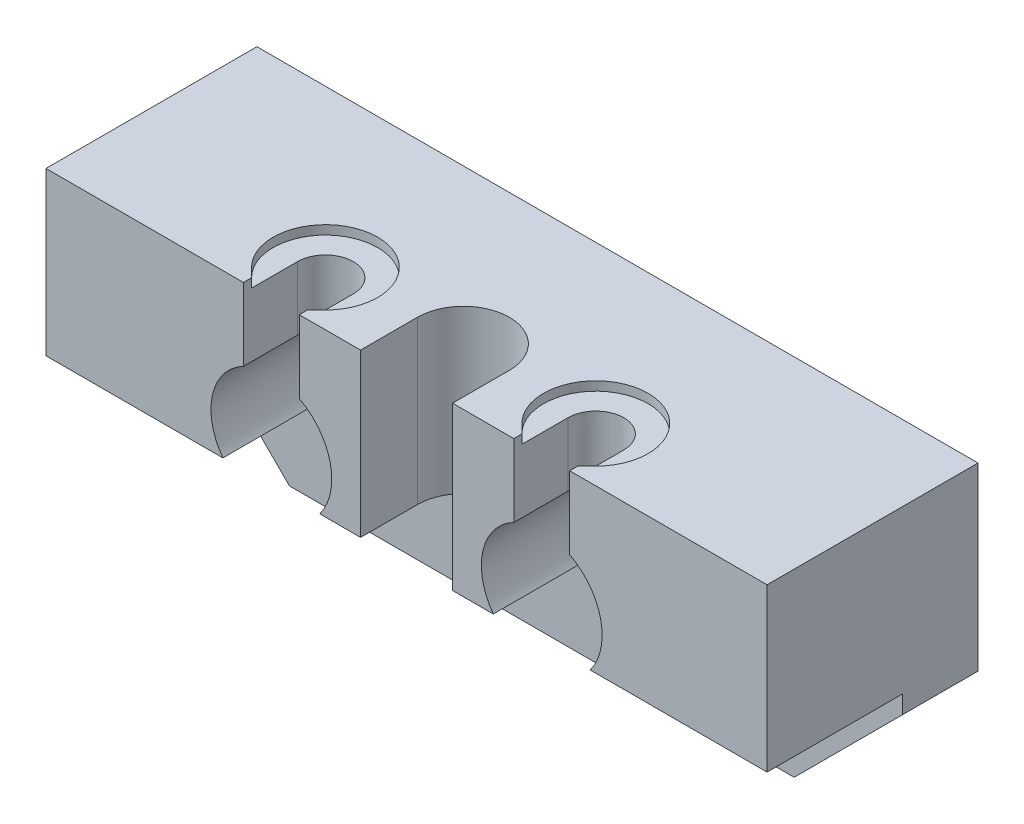
SolidWorks part; units mm, degrees
ref_plane "Front Plane" through (0, 0, 0) normal (0, 0, 1) x (1, 0, 0)
ref_plane "Top Plane" through (0, 0, 0) normal (0, 1, 0) x (1, 0, 0)
ref_plane "Right Plane" through (0, 0, 0) normal (1, 0, 0) x (0, 0, -1)
sketch "Sketch1" plane through (0, 0, 0) normal (0, 0, 1) x (1, 0, 0)
  line L1 (-20, 0) -> (20, 0)
  line L2 (-20, 0) -> (-20, 16)
  line L3 (-20, 16) -> (20, 16)
  line L4 (20, 0) -> (20, 16)
  dimension "D2" = 40
  dimension "D3" = 16
extrude "Boss-Extrude1" add sketch "Sketch1" along normal blind 12
sketch "Sketch2" plane through (0, 0, 12) normal (0, 0, 1) x (1, 0, 0)
  line L0 (0, 8) -> (0, 9) construction
  line L2 (-7.5, 9) -> (7.5, 9) construction
  line L3 (20, 16) -> (-20, 16) construction
  line L4 (-7.5, 5) -> (-7.5, 13) construction
  line L5 (-9.05, 5) -> (-9.05, 13) construction
  line L6 (-5.95, 5) -> (-5.95, 13) construction
  line L7 (7.5, 5) -> (7.5, 13) construction
  line L8 (5.95, 5) -> (5.95, 13) construction
  line L9 (9.05, 5) -> (9.05, 13) construction
  line L10 (-16, 8) -> (16, 8) construction
  arc A0 (-9.05, 5) -> (-5.95, 5) centre (-7.5, 5) ccw construction
  arc A1 (-5.95, 13) -> (-9.05, 13) centre (-7.5, 13) ccw construction
  arc A2 (5.95, 5) -> (9.05, 5) centre (7.5, 5) ccw construction
  arc A3 (9.05, 13) -> (5.95, 13) centre (7.5, 13) ccw construction
  circle A4 centre (-16, 8) radius 1.7784 construction
  circle A5 centre (16, 8) radius 1.7784 construction
  circle A6 centre (-7.5, 9) radius 1.55
  circle A7 centre (7.5, 9) radius 1.55
  point P8 (-7.5, 9)
  point P15 (7.5, 9)
  dimension "D1" = 1.55
  dimension "D2" = 8
  dimension "D3" = 7
  dimension "D4" = 15
  dimension "D5" = 1
  dimension "D6" = 32
extrude "Cut-Extrude1" cut sketch "Sketch2" against normal through all
sketch "Sketch5" plane through (0, 16, 0) normal (0, 1, 0) x (1, 0, 0)
  line L0 (0, 0) -> (0, -9) construction
  line L1 (-7.5, -9) -> (7.5, -9) construction
  line L2 (20, -12) -> (-20, -12) construction
  line L3 (-9.05, -9) -> (-9.05, -12)
  line L4 (-9.05, -12) -> (-5.95, -12)
  line L5 (-5.95, -12) -> (-5.95, -9)
  line L6 (5.95, -9) -> (5.95, -12)
  line L7 (5.95, -12) -> (9.05, -12)
  line L8 (9.05, -12) -> (9.05, -9)
  arc A0 (-5.95, -9) -> (-9.05, -9) centre (-7.5, -9) ccw
  arc A1 (9.05, -9) -> (5.95, -9) centre (7.5, -9) ccw
  dimension "D2" = 3.1
  dimension "D1" = 15
  dimension "D3" = 3
extrude "Cut-Extrude4" cut sketch "Sketch5" against normal through all
ref_axis "Axis1" through (7.5, 9, 9) along (0, 1, 0)
sketch "Sketch6" plane through (20, 0, 0) normal (1, 0, 0) x (0, 0, -1)
  line L0 (-12, 7) -> (-4.5, 7)
  line L3 (-4.5, 7) -> (-4.5, 0)
  line L4 (-12, 0) -> (0, 0) construction
  line L5 (-4.5, 0) -> (-12, 0)
  line L6 (-12, 0) -> (-12, 7)
  line L8 (-12, 16) -> (0, 16) construction
  line L9 (0, 0) -> (0, 16) construction
  dimension "D1" = 9
  dimension "D2" = 4.5
extrude "Cut-Extrude5" cut sketch "Sketch6" against normal through all
sketch "Sketch7" plane through (0, 16, 0) normal (0, 1, 0) x (1, 0, 0)
  line L1 (-9.5506, -11.0506) -> (-7.5, -13.1012)
  line L2 (-7.5, -13.1012) -> (-5.4494, -11.0506)
  line L3 (0, 0) -> (0, -12) construction
  line L4 (20, 0) -> (-20, 0) construction
  line L6 (7.5, -13.1012) -> (5.4494, -11.0506)
  line L7 (9.5506, -11.0506) -> (7.5, -13.1012)
  arc A0 (-5.4494, -11.0506) -> (-9.5506, -11.0506) centre (-7.5, -9) ccw
  arc A1 (5.4494, -11.0506) -> (9.5506, -11.0506) centre (7.5, -9) cw
  dimension "D1" = 5.8
extrude "Cut-Extrude6" cut sketch "Sketch7" against normal blind 0.5
chamfer "Chamfer4" [suppressed] distance 1.8 angle 45
sketch "Sketch8" plane through (0, 16, 0) normal (0, 1, 0) x (1, 0, 0)
  line L0 (-2.55, -8.8461) -> (-2.55, -12)
  line L1 (6.3988, -12) -> (-6.3988, -12) construction
  line L2 (-2.55, -12) -> (2.55, -12)
  line L3 (2.55, -12) -> (2.55, -8.8461)
  arc A0 (2.55, -9.0461) -> (-2.55, -9.0461) centre (0, -9.0461) ccw construction
  arc A1 (2.55, -8.8461) -> (-2.55, -8.8461) centre (0, -8.8461) ccw
  dimension "D1" = 2.55
  dimension "D2" = 0.2
extrude "Cut-Extrude7" cut sketch "Sketch8" against normal through all
sketch "Sketch9" plane through (0, 0, 12) normal (0, 0, 1) x (1, 0, 0)
  circle A0 centre (-7.5, 9) radius 3.35
  circle A1 centre (7.5, 9) radius 3.35
  dimension "D1" = 6.7
extrude "Cut-Extrude8" cut sketch "Sketch9" against normal up to surface (7.5 mm away) up to face at (0, 3.5, 4.5)
chamfer "Chamfer5" distance 1.8 angle 45 2 edges at (-7.5, 10.55, 4.5) (7.5, 10.55, 4.5)
chamfer "Chamfer6" distance 6 angle 45 2 edges at (20, 0, 2.25) (-20, 0, 2.25)
chamfer "Chamfer7" distance 0.3 angle 45 8 edges at (0, 16, 0) (-20, 11, 0) (-17, 3, 0) (0, 0, 0) (17, 3, 0) (20, 11, 0) (-5.95, 9, 0) (9.05, 9, 0)
sketch "Sketch10" plane through (0, 15.5, 0) normal (0, 1, 0) x (1, 0, 0)
  circle A0 centre (7.5, -9) radius 2.9
  circle A1 centre (-7.5, -9) radius 2.9
  arc A4 (-5.4494, -11.0506) -> (-9.5506, -11.0506) centre (-7.5, -9) ccw construction
  arc A5 (9.5506, -11.0506) -> (5.4494, -11.0506) centre (7.5, -9) ccw construction
  dimension "D1" = 5.8
extrude "Cut-Extrude9" [suppressed] cut sketch "Sketch10" against normal blind 0.5
